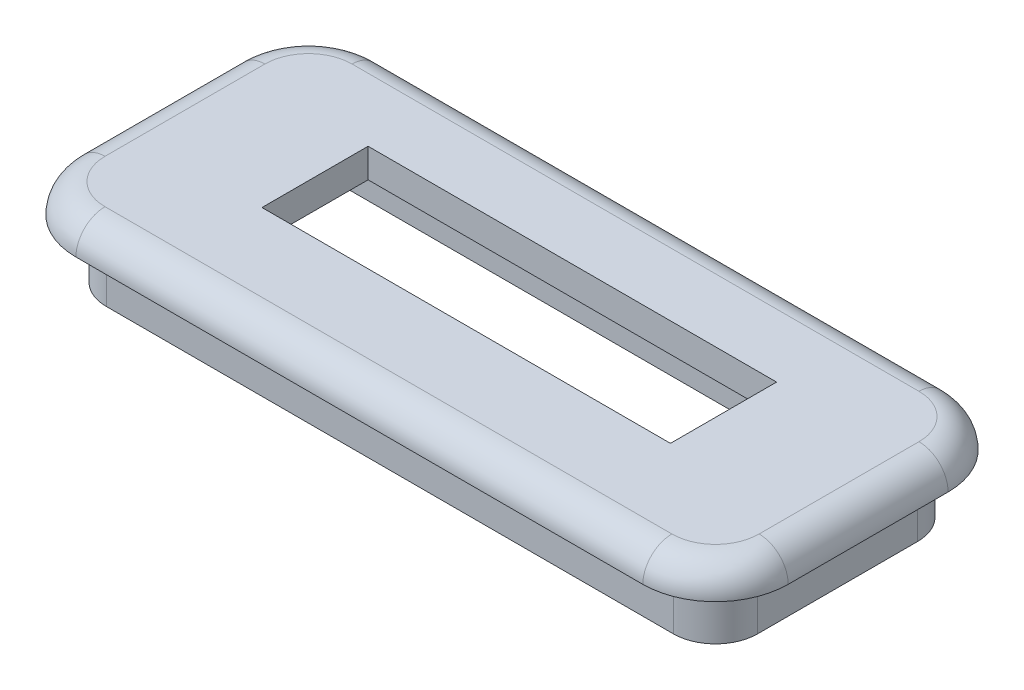
SolidWorks part; units mm, degrees
ref_plane "Front Plane" through (0, 0, 0) normal (0, 0, 1) x (1, 0, 0)
ref_plane "Top Plane" through (0, 0, 0) normal (0, 1, 0) x (1, 0, 0)
ref_plane "Right Plane" through (0, 0, 0) normal (1, 0, 0) x (0, 0, -1)
sketch "Sketch1" plane through (0, 0, 0) normal (0, 1, 0) x (1, 0, 0)
  line L1 (-19.5, 10.5) -> (19.5, 10.5)
  line L2 (-24.5, 5.5) -> (-24.5, -5.5)
  line L3 (-19.5, -10.5) -> (19.5, -10.5)
  line L4 (24.5, 5.5) -> (24.5, -5.5)
  line L5 (-24.5, 10.5) -> (24.5, -10.5) construction
  line L6 (-24.5, -10.5) -> (24.5, 10.5) construction
  arc A0 (-24.5, -5.5) -> (-19.5, -10.5) centre (-19.5, -5.5) ccw
  arc A1 (19.5, -10.5) -> (24.5, -5.5) centre (19.5, -5.5) ccw
  arc A2 (19.5, 10.5) -> (24.5, 5.5) centre (19.5, 5.5) cw
  arc A3 (-19.5, 10.5) -> (-24.5, 5.5) centre (-19.5, 5.5) ccw
  point P0 (0, 0)
  dimension "D3" = 5
  dimension "D1" = 49
  dimension "D2" = 21
extrude "Boss-Extrude1" add sketch "Sketch1" along normal blind 2
sketch "Sketch2" plane through (0, 0, 0) normal (0, -1, 0) x (1, 0, 0)
  line L8 (-20.9, 5.5) -> (-20.9, -5.5)
  line L9 (-19.5, -6.9) -> (19.5, -6.9)
  line L10 (20.9, -5.5) -> (20.9, 5.5)
  line L11 (19.5, 6.9) -> (-19.5, 6.9)
  line L12 (-22.4, 5.5) -> (-22.4, -5.5)
  line L13 (-19.5, -8.4) -> (19.5, -8.4)
  line L14 (22.4, -5.5) -> (22.4, 5.5)
  line L15 (19.5, 8.4) -> (-19.5, 8.4)
  line L16 (-22.4, 5.5) -> (-22.4, -5.5)
  line L17 (-19.5, -8.4) -> (19.5, -8.4)
  line L18 (22.4, -5.5) -> (22.4, 5.5)
  line L19 (19.5, 8.4) -> (-19.5, 8.4)
  arc A8 (-19.5, 6.9) -> (-20.9, 5.5) centre (-19.5, 5.5) ccw
  arc A9 (-20.9, -5.5) -> (-19.5, -6.9) centre (-19.5, -5.5) ccw
  arc A10 (19.5, -6.9) -> (20.9, -5.5) centre (19.5, -5.5) ccw
  arc A11 (20.9, 5.5) -> (19.5, 6.9) centre (19.5, 5.5) ccw
  arc A12 (-19.5, 8.4) -> (-22.4, 5.5) centre (-19.5, 5.5) ccw
  arc A13 (-22.4, -5.5) -> (-19.5, -8.4) centre (-19.5, -5.5) ccw
  arc A14 (19.5, -8.4) -> (22.4, -5.5) centre (19.5, -5.5) ccw
  arc A15 (22.4, 5.5) -> (19.5, 8.4) centre (19.5, 5.5) ccw
  arc A16 (-19.5, 8.4) -> (-22.4, 5.5) centre (-19.5, 5.5) ccw
  arc A17 (-22.4, -5.5) -> (-19.5, -8.4) centre (-19.5, -5.5) ccw
  arc A18 (19.5, -8.4) -> (22.4, -5.5) centre (19.5, -5.5) ccw
  arc A19 (22.4, 5.5) -> (19.5, 8.4) centre (19.5, 5.5) ccw
  dimension "D1" = 2.1
  dimension "D2" = 1.5
extrude "Boss-Extrude2" add sketch "Sketch2" along normal blind 4
sketch "Sketch3" plane through (0, 2, 0) normal (0, 1, 0) x (1, 0, 0)
  line L0 (0, 20.1438) -> (0, -20.5977) construction
  line L1 (19.5, 10.5) -> (-19.5, 10.5) construction
  line L2 (-14.05, 4.15) -> (14.05, 4.15)
  line L3 (-14.05, 4.15) -> (-14.05, -3.15)
  line L4 (-14.05, -3.15) -> (14.05, -3.15)
  line L5 (14.05, 4.15) -> (14.05, -3.15)
  line L6 (-14.05, 4.15) -> (14.05, -3.15) construction
  line L7 (-14.05, -3.15) -> (14.05, 4.15) construction
  point P3 (0, 0.5)
  dimension "D1" = 28.1
  dimension "D2" = 7.3
  dimension "D3" = 10
extrude "Cut-Extrude1" cut sketch "Sketch3" against normal blind 4
fillet "Fillet1" radius 2 8 edges at (-23.0355, 2, -9.0355) (0, 2, -10.5) (23.0355, 2, -9.0355) (24.5, 2, 0) (23.0355, 2, 9.0355) (0, 2, 10.5) (-23.0355, 2, 9.0355) (-24.5, 2, 0)
